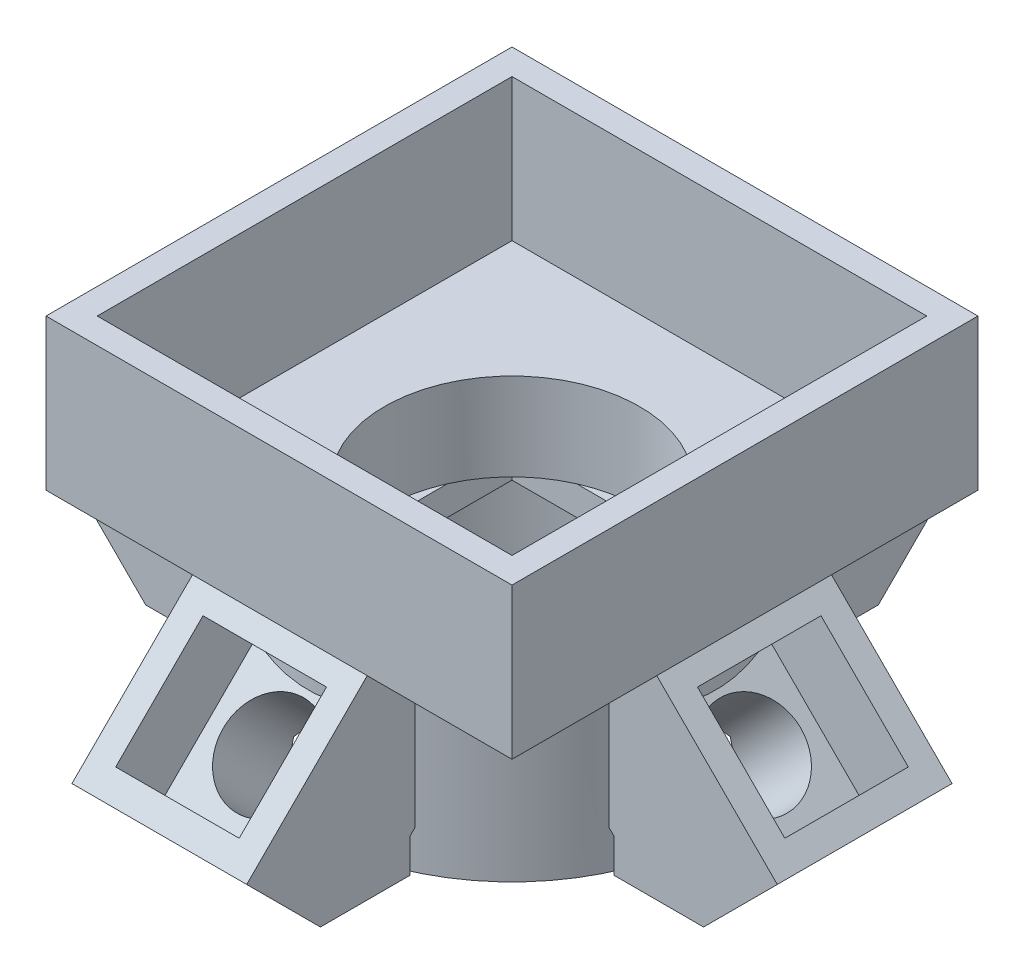
SolidWorks part; units mm, degrees
material "AISI 321 Annealed Stainless Steel (SS)"
ref_plane "前视基准面" through (0, 0, 0) normal (0, 0, 1) x (1, 0, 0)
ref_plane "上视基准面" through (0, 0, 0) normal (0, 1, 0) x (1, 0, 0)
ref_plane "右视基准面" through (0, 0, 0) normal (1, 0, 0) x (0, 0, -1)
other "Configuration Table"
sketch "Sketch6" plane through (0, 0, 0) normal (0, 1, 0) x (1, 0, 0)
  circle A0 centre (0, 0) radius 2.19
  circle A1 centre (0, 0) radius 3
  dimension "D1" = 4.38
  dimension "D2" = 6
extrude "Boss-Extrude3" add sketch "Sketch6" along normal blind 2
sketch "Sketch7" plane through (0, 0, 0) normal (0, -1, 0) x (-1, 0, 0)
  line L1 (-2, -2) -> (2, -2)
  line L2 (-2, -2) -> (-2, 2)
  line L3 (-2, 2) -> (2, 2)
  line L4 (2, -2) -> (2, 2)
  line L5 (-2, -2) -> (2, 2) construction
  line L6 (-2, 2) -> (2, -2) construction
  line L11 (-2.25, -2.25) -> (2.25, 2.25) construction
  line L12 (-2.25, 2.25) -> (2.25, -2.25) construction
  point P0 (0, 0)
  point P6 (0, 0)
  dimension "D1" = 4
  dimension "D2" = 4
  dimension "D4" = 4.5
extrude "Cut-Extrude2" cut sketch "Sketch7" against normal blind 0.5
sketch "Sketch8" plane through (0, 0.5, 0) normal (0, -1, 0) x (-1, 0, 0)
  line L0 (-0.8922, 2) -> (0.8922, 2)
  line L5 (-2, 0.8922) -> (-2, -0.8922)
  line L6 (-0.8922, -2) -> (0.8922, -2)
  line L7 (2, 0.8922) -> (2, -0.8922)
  arc A4 (-2, 0.8922) -> (-2, -0.8922) centre (0, 0) ccw
  arc A5 (0.8922, 2) -> (-0.8922, 2) centre (0, 0) ccw
  arc A6 (-0.8922, -2) -> (0.8922, -2) centre (0, 0) ccw
  arc A7 (2, -0.8922) -> (2, 0.8922) centre (0, 0) ccw
extrude "Boss-Extrude5" add sketch "Sketch8" along normal blind 0.5
sketch "Sketch9" plane through (0, 0, 0) normal (0, 0, 1) x (1, 0, 0)
  line L0 (0, 2.7565) -> (0, -2.7704) construction
  line L1 (-3.7455, 0) -> (3.8358, 0) construction
  line L2 (2.19, 2.4224) -> (2.19, 0) construction
  line L3 (-2.19, 2) -> (-2.19, 0) construction
sketch "Sketch13" plane through (0, 0, 0) normal (0, -1, 0) x (-1, 0, 0)
  line L0 (-2, 2) -> (2, -2) construction
sketch "Sketch17" plane through (0, 0, 0) normal (0, -1, 0) x (-1, 0, 0)
  line L0 (-2, 2) -> (2, -2) construction
  circle A0 centre (0, 0) radius 3
  circle A1 centre (0, 0) radius 3.5
  dimension "D1" = 6
  dimension "D2" = 0.5
extrude "Boss-Extrude11" add sketch "Sketch17" against normal blind 0.5
sketch "Sketch18" plane through (0, 0, 0) normal (0, -1, 0) x (-1, 0, 0)
  circle A0 centre (0, 0) radius 3.1
  circle A1 centre (0, 0) radius 3.5
  dimension "D1" = 6.2
  dimension "D2" = 7
extrude "Boss-Extrude12" add sketch "Sketch18" along normal blind 2
sketch "Sketch19" plane through (0, 0, 0) normal (0, 0, 1) x (1, 0, 0)
  line L1 (2.19, 2.4224) -> (2.19, 0) construction
  line L2 (4.2889, -2) -> (5.1213, -1.1675)
  line L3 (5.1213, -1.1675) -> (3, 0.9538)
  line L4 (3, 0.5) -> (3, 2) construction
  line L5 (3, 0.9538) -> (2.19, 0.1438)
  line L8 (2.19, 0.1438) -> (3.2507, -0.9169)
  line L10 (4.2889, -2) -> (4.0338, -2)
  line L12 (4.0338, -2) -> (3.2507, -2)
  line L13 (3.2507, -2) -> (3.2507, -0.9169)
  line L14 (-3.5, -2) -> (3.5, -2) construction
  dimension "D1" = 3
  dimension "D2" = 0
  dimension "D3" = 135
  dimension "D4" = 45
  dimension "D5" = 90
  dimension "D6" = 135
  dimension "D7" = 1.8562
  dimension "D8" = 1.5
extrude "Boss-Extrude13" add sketch "Sketch19" along normal blind 1.5 and the other way blind 1.5
sketch "Sketch29" plane through (1.9769, 1.9769, 0) normal (0.7071, 0.7071, 0) x (0, 0, -1)
  line L0 (1.5, -1.4469) -> (0, -1.4469) construction
  line L1 (1.5, -4.4469) -> (-1.5, -4.4469)
  line L2 (1.5, -4.4469) -> (1.5, -1.4469)
  line L3 (1.5, -1.4469) -> (-1.5, -1.4469)
  line L4 (-1.5, -4.4469) -> (-1.5, -1.4469)
  line L5 (-1.5, -1.8825) -> (-1.5, -2.8219) construction
  dimension "D1" = 0
  dimension "D2" = 0
extrude "Boss-Extrude16" add sketch "Sketch29" along normal blind 1.5
sketch "Sketch30" plane through (3.0376, 3.0376, 0) normal (0.7071, 0.7071, 0) x (0, 0, -1)
  line L0 (1.5, -1.4469) -> (-1.5, -1.4469) construction
  line L1 (-1.06, -1.8869) -> (1.06, -1.8869)
  line L2 (-1.06, -1.8869) -> (-1.06, -4.0069)
  line L3 (-1.06, -4.0069) -> (1.06, -4.0069)
  line L4 (1.06, -1.8869) -> (1.06, -4.0069)
  line L5 (-1.5, -4.4469) -> (1.5, -4.4469) construction
  line L6 (-1.5, -1.4469) -> (-1.5, -4.4469) construction
  line L7 (1.5, -4.4469) -> (1.5, -1.4469) construction
  dimension "D1" = 0.44
  dimension "D2" = 0.44
  dimension "D3" = 0.44
  dimension "D4" = 0.44
extrude "Cut-Extrude10" cut sketch "Sketch30" against normal up to surface (2.6455 mm away) up to face at (2.6201, -0.2863, 0)
sketch "Sketch31" plane through (1.1669, 1.1669, 0) normal (-0.7071, -0.7071, 0) x (0, 0, 1)
  line L0 (-1.06, -2.4696) -> (-1.06, -1.8869) construction
  line L1 (-1.16, -1.7869) -> (1.06, -1.7869)
  line L2 (-1.16, -1.7869) -> (-1.16, -4.0069)
  line L3 (-1.16, -4.0069) -> (1.06, -4.0069)
  line L4 (1.06, -1.7869) -> (1.06, -4.0069)
  line L5 (-1.06, -1.8869) -> (1.06, -1.8869) construction
  dimension "D1" = 0.1
  dimension "D2" = 0.1
  dimension "D3" = 2.22
  dimension "D4" = 2.22
extrude "Boss-Extrude17" add sketch "Sketch31" against normal blind 1.27
sketch "Sketch32" plane through (2.0649, 2.0649, 0) normal (0.7071, 0.7071, 0) x (0, 0, -1)
  line L0 (-1.06, -4.0069) -> (1.06, -4.0069) construction
  line L1 (1.06, -4.0069) -> (1.06, -1.8869) construction
  circle A0 centre (0, -2.9469) radius 0.81
  dimension "D1" = 1.62
  dimension "D2" = 1.06
  dimension "D3" = 1.06
extrude "Cut-Extrude11" cut sketch "Sketch32" against normal through all both and the other way through all
ref_point "Point3"
sketch "Sketch33" plane through (3.0376, 3.0376, 0) normal (0.7071, 0.7071, 0) x (0, 0, -1)
  line L0 (1.5, -4.4469) -> (1.5, -1.4469) construction
  line L1 (1.6, -1.3469) -> (-1.6, -1.3469)
  line L2 (1.6, -1.3469) -> (1.6, -4.5469)
  line L3 (1.6, -4.5469) -> (-1.6, -4.5469)
  line L4 (-1.6, -1.3469) -> (-1.6, -4.5469)
  line L5 (1.5, -1.4469) -> (-1.5, -1.4469) construction
  line L6 (-1.5, -4.4469) -> (1.5, -4.4469) construction
  dimension "D1" = 0.1
  dimension "D2" = 0.1
  dimension "D3" = 0.1
  dimension "D4" = 3.2
extrude "Cut-Extrude12" cut sketch "Sketch33" against normal blind 0.18
pattern_circular "CirPattern3" count 4 over 360 about axis through (0, 0, 0) along (0, 1, 0) of "Boss-Extrude13", "Boss-Extrude16"
sketch "Sketch34" plane through (-3.0376, 3.0376, 0) normal (-0.7071, 0.7071, 0) x (0, 0, 1)
  line L0 (1.5, -1.4469) -> (-1.5, -1.4469) construction
  line L1 (-1.07, -1.8669) -> (1.07, -1.8669)
  line L2 (-1.07, -1.8669) -> (-1.07, -4.0269)
  line L3 (-1.07, -4.0269) -> (1.07, -4.0269)
  line L4 (1.07, -1.8669) -> (1.07, -4.0269)
  line L5 (-1.5, -4.4469) -> (1.5, -4.4469) construction
  line L6 (1.5, -4.4469) -> (1.5, -1.4469) construction
  line L7 (-1.5, -1.4469) -> (-1.5, -4.4469) construction
  dimension "D1" = 0.42
  dimension "D2" = 0.42
  dimension "D3" = 0.43
  dimension "D4" = 0.43
extrude "Cut-Extrude13" cut sketch "Sketch34" against normal up to surface (2.6455 mm away) up to face at (-2.6201, -0.2863, 0)
sketch "Sketch35" plane through (0, 3.0376, -3.0376) normal (0, 0.7071, -0.7071) x (1, 0, 0)
  line L0 (1.5, 4.4469) -> (-1.5, 4.4469) construction
  line L1 (-1.06, 4.0069) -> (1.06, 4.0069)
  line L2 (-1.06, 4.0069) -> (-1.06, 1.8869)
  line L3 (-1.06, 1.8869) -> (1.06, 1.8869)
  line L4 (1.06, 4.0069) -> (1.06, 1.8869)
  line L5 (-1.5, 4.4469) -> (-1.5, 1.4469) construction
  line L6 (1.5, 1.4469) -> (1.5, 4.4469) construction
  line L7 (-1.5, 1.4469) -> (1.5, 1.4469) construction
  dimension "D1" = 0.44
  dimension "D2" = 0.44
  dimension "D3" = 0.44
  dimension "D4" = 0.44
extrude "Cut-Extrude14" cut sketch "Sketch35" against normal up to surface (2.6455 mm away) up to face at (0, -0.2863, -2.6201)
sketch "Sketch36" plane through (0, 3.0376, 3.0376) normal (0, 0.7071, 0.7071) x (1, 0, 0)
  line L0 (-1.5, -1.8825) -> (-1.5, -2.8219) construction
  line L1 (-1.06, -1.8869) -> (1.06, -1.8869)
  line L2 (-1.06, -1.8869) -> (-1.06, -4.0069)
  line L3 (-1.06, -4.0069) -> (1.06, -4.0069)
  line L4 (1.06, -1.8869) -> (1.06, -4.0069)
  line L5 (-1.5, -4.4469) -> (1.5, -4.4469) construction
  line L6 (1.5, -4.4469) -> (1.5, -1.4469) construction
  line L7 (1.5, -1.4469) -> (-1.5, -1.4469) construction
  dimension "D1" = 0.44
  dimension "D2" = 0.44
  dimension "D3" = 0.44
  dimension "D4" = 0.44
extrude "Cut-Extrude15" cut sketch "Sketch36" against normal up to surface (2.6455 mm away) up to face at (0, -0.2863, 2.6201)
pattern_circular "CirPattern16" count 4 over 360 about axis through (0, 0, 0) along (0, 1, 0) of "Boss-Extrude17", "Cut-Extrude11", "Cut-Extrude12"
sketch "Sketch37" plane through (0, -2, 0) normal (0, -1, 0) x (1, 0, 0)
  circle A1 centre (0, 0) radius 10
  dimension "D2" = 20
extrude "Cut-Extrude17" cut sketch "Sketch37" against normal blind 0.5 contours A1
sketch "Sketch38" plane through (0, 0.5, 0) normal (0, 1, 0) x (1, 0, 0)
  circle A0 centre (0, 0) radius 3.5
  circle A1 centre (0, 0) radius 2.85
  dimension "D1" = 7
  dimension "D2" = 5.7
extrude "Boss-Extrude18" add sketch "Sketch38" along normal up to surface (1.5 mm away) up to face at (0, 2, 3)
sketch "Sketch39" plane through (0, 2.0649, -2.0649) normal (0, 0.7071, -0.7071) x (1, 0, 0)
  line L1 (-1.06, 4.0069) -> (1.06, 4.0069)
  line L2 (-1.06, 4.0069) -> (-1.06, 1.8869)
  line L3 (-1.06, 1.8869) -> (1.06, 1.8869)
  line L4 (1.06, 4.0069) -> (1.06, 1.8869)
extrude "Cut-Extrude18" cut sketch "Sketch39" along normal blind 0.5
sketch "Sketch40" plane through (0, 2, 0) normal (0, 1, 0) x (1, 0, 0)
  line L1 (-3.5, 3.5) -> (3.5, 3.5)
  line L2 (-3.5, 3.5) -> (-3.5, -3.5)
  line L3 (-3.5, -3.5) -> (3.5, -3.5)
  line L4 (3.5, 3.5) -> (3.5, -3.5)
  line L5 (-4, 4) -> (4, 4)
  line L6 (-4, 4) -> (-4, -4)
  line L7 (-4, -4) -> (4, -4)
  line L8 (4, 4) -> (4, -4)
  dimension "D1" = 3.5
  dimension "D2" = 3.5
  dimension "D3" = 3.5
  dimension "D4" = 3.5
  dimension "D5" = 0.5
  dimension "D6" = 0.5
  dimension "D7" = 0.5
  dimension "D8" = 0.5
extrude "Boss-Extrude19" add sketch "Sketch40" along normal blind 2.44 separate body
sketch "Sketch41" plane through (0, 2, 0) normal (0, -1, 0) x (1, 0, 0)
  line L1 (-4, 4) -> (4, 4)
  line L2 (-4, 4) -> (-4, -4)
  line L3 (-4, -4) -> (4, -4)
  line L4 (4, 4) -> (4, -4)
  circle A0 centre (0, 0) radius 2.19
  dimension "D1" = 4.38
extrude "Boss-Extrude20" add sketch "Sketch41" along normal blind 0.15
sketch "Sketch42" plane through (0, 1.85, 0) normal (0, -1, 0) x (1, 0, 0)
  line L1 (-4, 4) -> (4, 4)
  line L2 (-4, 4) -> (-4, -4)
  line L3 (-4, -4) -> (4, -4)
  line L4 (4, 4) -> (4, -4)
  circle A0 centre (0, 0) radius 2.19
  dimension "D1" = 4.38
extrude "Boss-Extrude21" add sketch "Sketch42" along normal up to vertex (0.7339 mm away) draft 45
sketch "Sketch43" plane through (0, 2, 0) normal (0, 1, 0) x (1, 0, 0)
  line L1 (-3.56, 3.56) -> (3.56, 3.56)
  line L2 (-3.56, 3.56) -> (-3.56, -3.56)
  line L3 (-3.56, -3.56) -> (3.56, -3.56)
  line L4 (3.56, 3.56) -> (3.56, -3.56)
  line L5 (-3.56, 3.56) -> (3.56, -3.56) construction
  line L6 (-3.56, -3.56) -> (3.56, 3.56) construction
  point P0 (0, 0)
  dimension "D1" = 7.12
  dimension "D2" = 7.12
extrude "Cut-Extrude19" cut sketch "Sketch43" along normal blind 10
